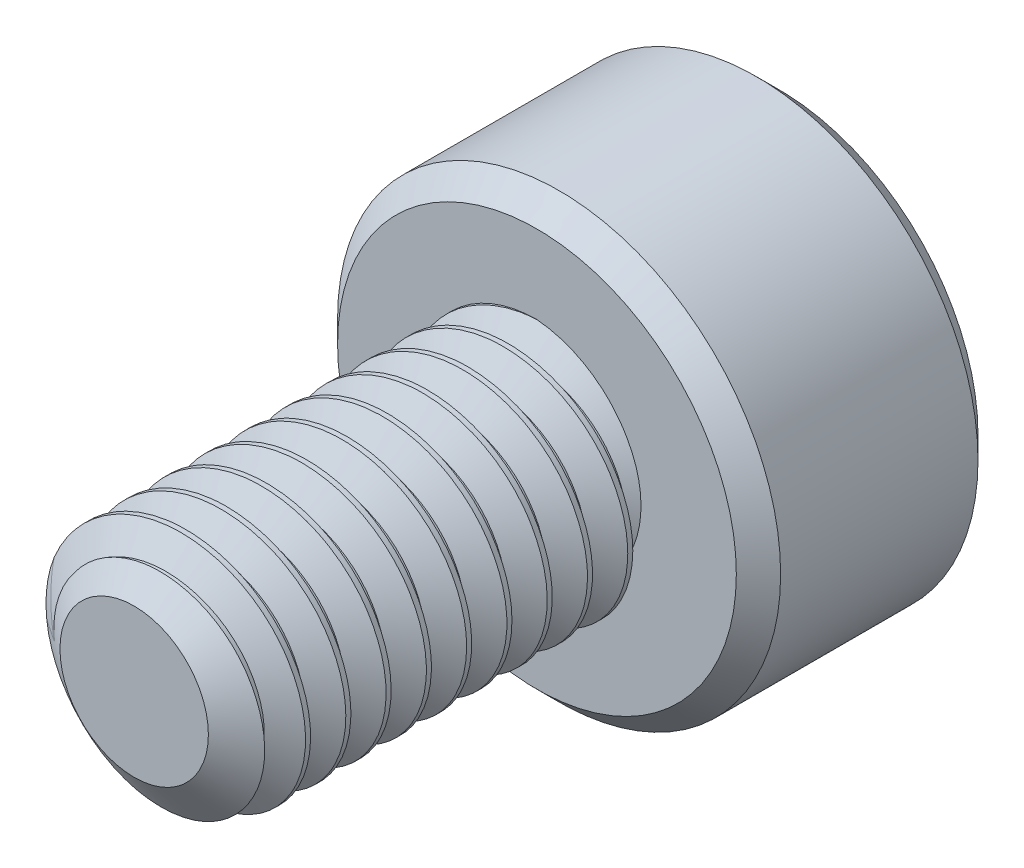
SolidWorks part; units mm, degrees
other "DetailItem1"
ref_plane "Front Plane" through (0, 0, 0) normal (0, 0, 1) x (1, 0, 0)
ref_plane "Top Plane" through (0, 0, 0) normal (0, 1, 0) x (1, 0, 0)
ref_plane "Right Plane" through (0, 0, 0) normal (1, 0, 0) x (0, 0, -1)
sketch "Sketch1" plane through (0, 0, 0) normal (0, 0, 1) x (1, 0, 0)
  circle A0 centre (0, 0) radius 1.5
  dimension "OD" = 3
extrude "Extrude1" add sketch "Sketch1" against normal blind 5
sketch "Sketch2" plane through (0, 0, 0) normal (0, 0, 1) x (1, 0, 0)
  circle A0 centre (0, 0) radius 1.5 construction
  circle A1 centre (0, 0) radius 1.5
curve "Helix/Spiral1" pitch 0.5 height 5.5 radius 1.5 centre (0, 0, 0) axis (0, 0, -1) start towards (0, 1, 0) parameters "pitch"=0.5
sketch "Sketch3" plane through (0, 0, 0) normal (1, 0, 0) x (0, 0, -1)
  line L0 (-0.4375, 1.5) -> (-0.25, 1.1752)
  line L1 (-0.25, 1.1752) -> (-0.1875, 1.1752)
  line L2 (-0.1875, 1.1752) -> (0, 1.5)
  line L3 (-0.4375, 1.5) -> (0, 1.5)
  line L4 (-0.2187, 1.5) -> (-0.2188, 1.1752) construction
  line L5 (-0.3438, 1.3376) -> (-0.0938, 1.3376) construction
  line L6 (0, 1.5) -> (0, -1.5) construction
  dimension "D2" = 0.25
  dimension "D3" = 60
sweep "Cut-Sweep1" cut profiles "Sketch3" path "Helix/Spiral1" align with end faces yes
sketch "Sketch4" plane through (0, 0, 0) normal (1, 0, 0) x (0, 0, -1)
  line L0 (0.4053, 1.5) -> (0, 0.9212)
  line L1 (0, 0.9212) -> (0, 1.5)
  line L2 (0.4053, 1.5) -> (0, 1.5)
  line L3 (-0.4375, 1.5) -> (0, 1.5) construction
  line L4 (0, 0) -> (7.0209, 0) construction
  dimension "D1" = 55
  dimension "D2" = 0.254
revolve "Cut-Revolve1" cut sketch "Sketch4" angle 360 about L4
sketch "Sketch6" plane through (0, 0, -5) normal (0, 0, -1) x (-1, 0, 0)
  circle A0 centre (0, 0) radius 2.75
  dimension "head dia" = 5.5
extrude "Extrude2" add sketch "Sketch6" along normal blind 3
sketch "Sketch7" plane through (0, 0, -8) normal (0, 0, -1) x (-1, 0, 0)
  line L1 (0, 1.4434) -> (-1.25, 0.7217)
  line L2 (-1.25, 0.7217) -> (-1.25, -0.7217)
  line L3 (-1.25, -0.7217) -> (0, -1.4434)
  line L4 (0, -1.4434) -> (1.25, -0.7217)
  line L5 (1.25, -0.7217) -> (1.25, 0.7217)
  line L6 (1.25, 0.7217) -> (0, 1.4434)
  circle A0 centre (0, 0) radius 1.25 construction
  dimension "hex dia" = 2.5
extrude "Cut-Extrude1" cut sketch "Sketch7" against normal blind 1.875
sketch "Sketch8" plane through (0, 0, -8) normal (0, 0, -1) x (-1, 0, 0)
  circle A0 centre (0, 0) radius 1.4434
extrude "Cut-Extrude2" cut sketch "Sketch8" against normal through all draft 45
chamfer "Chamfer1" distance 0.275 angle 45 2 edges at (-2.75, 0, -8) (-2.75, 0, -5)
sketch "Sketch10" plane through (0, 0, -5) normal (0, 0, 1) x (1, 0, 0)
  circle A1 centre (0, 0) radius 1.5
  circle A2 centre (0, 0) radius 1.5
  dimension "D1" = 0
ref_plane "Plane1" through (0, 0, 0) normal (0, 0, 1) x (1, 0, 0)
extrude "partial thread" [suppressed] add sketch "Sketch10" along normal up to surface (4 mm away) separate body up to plane "Plane1"
chamfer "Chamfer2" [suppressed] distance 0.06 angle 45
combine bodies "Combine1" [suppressed] operation type add bodies to combine 107 108
equation "\"D3@Helix/Spiral1\" = \"screw length@Extrude1\"+\"pitch@Helix/Spiral1\""
equation "\"D1@Sketch3\" = \"pitch@Helix/Spiral1\"*.125"
equation "\"D2@Sketch3\" = \"pitch@Helix/Spiral1\"*.5"
equation "\"D1@Cut-Extrude1\" = \"hex dia@Sketch7\"*.75"
equation "\"D1@Chamfer1\" = \"head dia@Sketch6\"*.05"
equation "\"D1@Sketch9\" = \"pitch@Helix/Spiral1\"*2.5"
equation "\"D1@Chamfer2\"=\"OD@Sketch1\"*.02"
